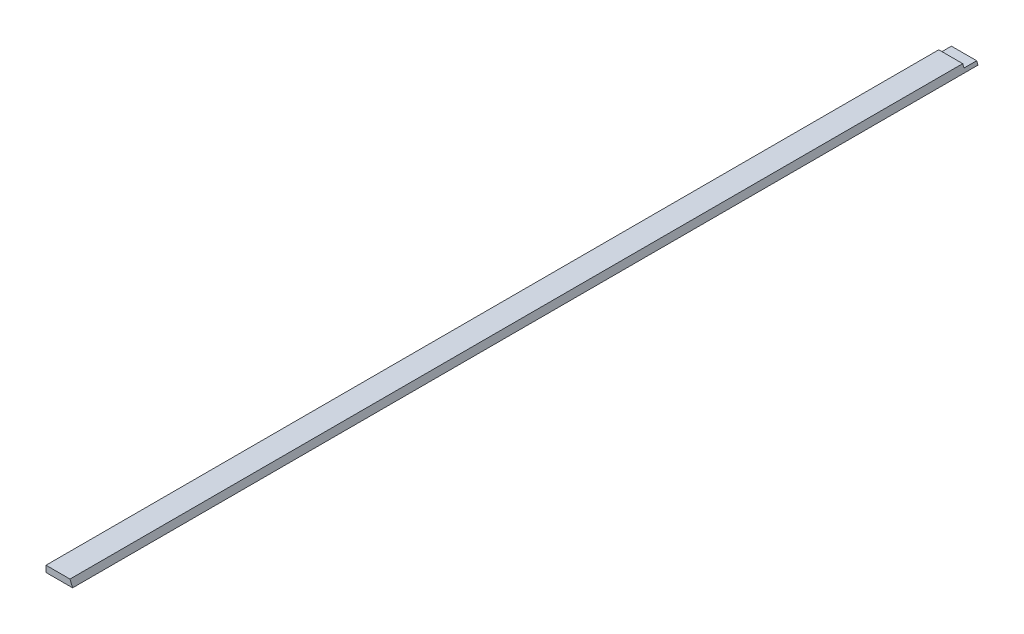
SolidWorks part; units mm, degrees
ref_plane "Front Plane" through (0, 0, 0) normal (0, 0, 1) x (1, 0, 0)
ref_plane "Top Plane" through (0, 0, 0) normal (0, 1, 0) x (1, 0, 0)
ref_plane "Right Plane" through (0, 0, 0) normal (1, 0, 0) x (0, 0, -1)
sketch "Sketch1" plane through (0, 0, 0) normal (0, 0, 1) x (1, 0, 0)
  line L0 (0, 0) -> (0, 6.35)
  line L1 (0, 6.35) -> (24.0397, 6.35)
  line L2 (24.0397, 6.35) -> (26.67, 0)
  line L3 (26.67, 0) -> (0, 0)
  dimension "D1" = 67.5
  dimension "D2" = 26.67
  dimension "D3" = 6.35
extrude "Boss-Extrude1" add sketch "Sketch1" along normal blind 908.05
sketch "Sketch2" plane through (0, 6.35, 0) normal (0, 1, 0) x (1, 0, 0)
  line L0 (26.67, -908.05) -> (26.67, 0) construction
  line L1 (0, 0) -> (26.67, 0)
  line L2 (0, 0) -> (0, -12.7)
  line L3 (0, -12.7) -> (26.67, -12.7)
  line L4 (26.67, 0) -> (26.67, -12.7)
  dimension "D1" = 12.7
extrude "Cut-Extrude1" cut sketch "Sketch2" against normal blind 3.175
